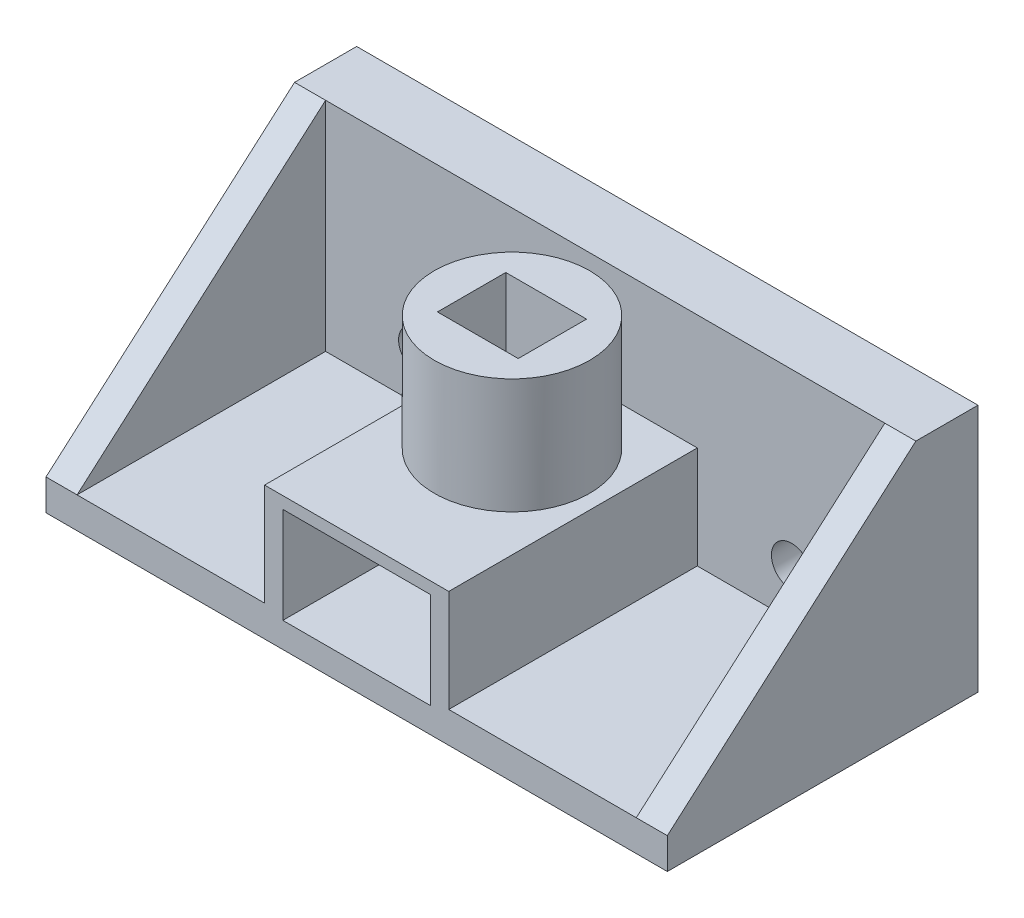
SolidWorks part; units mm, degrees
ref_plane "Front" through (0, 0, 0) normal (0, 0, 1) x (1, 0, 0)
ref_plane "Top" through (0, 0, 0) normal (0, 1, 0) x (1, 0, 0)
ref_plane "Right" through (0, 0, 0) normal (1, 0, 0) x (0, 0, -1)
sketch "Sketch1" plane through (0, 0, 0) normal (0, 1, 0) x (1, 0, 0)
  line L0 (-50, 25) -> (-50, 15)
  line L1 (-50, 25) -> (50, 25)
  line L2 (-50, 25) -> (-50, -25)
  line L3 (-50, -25) -> (50, -25)
  line L4 (50, 25) -> (50, -25)
  line L5 (-50, 25) -> (50, -25) construction
  line L6 (-50, -25) -> (50, 25) construction
  line L7 (-50, 15) -> (50, 15)
  line L8 (50, 15) -> (50, 25)
  line L9 (-50, 25) -> (50, 25)
  line L10 (-50, 15) -> (-50, 25)
  circle A0 centre (0, 0) radius 7.6
  point P0 (0, 0)
  dimension "D3" = 15.2
  dimension "D1" = 100
  dimension "D2" = 50
extrude "Boss-Extrude4" add sketch "Sketch1" along normal blind 5 contours L7 L2 L3 L4 region at (0, 0, -13.923)
sketch "Sketch9" plane through (0, 5, 0) normal (0, 1, 0) x (1, 0, 0)
  circle A0 centre (0, 0) radius 12.5
  dimension "D1" = 25
extrude "Boss-Extrude7" add sketch "Sketch9" along normal blind 35 contours A0
extrude "Extrude-Thin1" add sketch "Sketch1<7>" along normal blind 40 thin contours L1 thin type one direction wall 10
sketch "Sketch1<7>" plane through (0, 0, 0) normal (0, 1, 0) x (1, 0, 0) same geometry as "Sketch1"
sketch "Sketch5" plane through (50, 0, 0) normal (1, 0, 0) x (0, 0, -1)
  line L0 (15, 40) -> (15, 5)
  line L1 (15, 5) -> (-25, 5)
  line L2 (-25, 5) -> (15, 40)
extrude "Boss-Extrude5" add sketch "Sketch5" against normal blind 5
sketch "Sketch6" plane through (-50, 0, 0) normal (-1, 0, 0) x (0, 0, 1)
  line L0 (-15, 40) -> (-15, 5)
  line L1 (-15, 5) -> (25, 5)
  line L2 (25, 5) -> (-15, 40)
extrude "Boss-Extrude6" add sketch "Sketch6" against normal blind 5
sketch "Sketch11" plane through (0, 40, 0) normal (0, 1, 0) x (1, 0, 0)
  line L1 (6.5, -5.5) -> (-6.5, -5.5)
  line L2 (6.5, -5.5) -> (6.5, 5.5)
  line L3 (6.5, 5.5) -> (-6.5, 5.5)
  line L4 (-6.5, -5.5) -> (-6.5, 5.5)
  line L5 (6.5, -5.5) -> (-6.5, 5.5) construction
  line L6 (6.5, 5.5) -> (-6.5, -5.5) construction
  point P0 (0, 0)
  dimension "D1" = 13
  dimension "D2" = 11
extrude "Cut-Extrude2" cut sketch "Sketch11" against normal blind 15
sketch "Sketch13" plane through (0, 0, -25) normal (0, 0, -1) x (-1, 0, 0)
  line L0 (0, 40) -> (0, 12.5)
  line L1 (50, 40) -> (-50, 40) construction
  line L2 (0, 50) -> (0, -50) construction
  line L3 (0, 12.5) -> (30, 12.5)
  line L5 (50, 0) -> (-50, 0) construction
  circle A0 centre (30, 12.5) radius 3.25
  circle A1 centre (-30, 12.5) radius 3.25
  circle A2 centre (30, 12.5) radius 6
  circle A3 centre (-30, 12.5) radius 6
  dimension "D3" = 6.5
  dimension "D4" = 12
  dimension "D1" = 12.5
  dimension "D2" = 30
extrude "Cut-Extrude4" cut sketch "Sketch13<5>" against normal blind 205 contours A0
sketch "Sketch13<5>" plane through (0, 0, -25) normal (0, 0, -1) x (-1, 0, 0) same geometry as "Sketch13"
extrude "Cut-Extrude5" cut sketch "Sketch13" against normal blind 205 contours A1
sketch "Sketch15" plane through (0, 0, -25) normal (0, 0, -1) x (-1, 0, 0)
  line L0 (0, 40) -> (0, 24.3849)
  line L1 (50, 40) -> (-50, 40) construction
  line L2 (0, 50) -> (0, -50) construction
  line L4 (-14.8205, 21.4553) -> (14.8205, 21.4553)
  line L5 (-14.8205, 21.4553) -> (-14.8205, 2.1541)
  line L6 (-14.8205, 2.1541) -> (14.8205, 2.1541)
  line L7 (14.8205, 21.4553) -> (14.8205, 2.1541)
  line L8 (-14.8205, 21.4553) -> (14.8205, 2.1541) construction
  line L9 (-14.8205, 2.1541) -> (14.8205, 21.4553) construction
  line L10 (-11.8829, 19.5424) -> (11.8829, 19.5424)
  line L11 (-11.8829, 19.5424) -> (-11.8829, 4.067)
  line L12 (-11.8829, 4.067) -> (11.8829, 4.067)
  line L13 (11.8829, 19.5424) -> (11.8829, 4.067)
  line L14 (-11.8829, 19.5424) -> (11.8829, 4.067) construction
  line L15 (-11.8829, 4.067) -> (11.8829, 19.5424) construction
  point P7 (0, 11.8047)
  point P12 (0, 11.8047)
extrude "Boss-Extrude11" add sketch "Sketch15" against normal blind 50 contours L7 L4 L5 L6 L10 L13 L12 L11 region at (0, 21.1016, -25)
sketch "Sketch16" plane through (0, 0, -25) normal (0, 0, -1) x (-1, 0, 0)
  line L1 (11.8829, 19.5424) -> (-11.8829, 19.5424)
  line L2 (11.8829, 19.5424) -> (11.8829, 4.067)
  line L3 (11.8829, 4.067) -> (-11.8829, 4.067)
  line L4 (-11.8829, 19.5424) -> (-11.8829, 4.067)
extrude "Cut-Extrude6" cut sketch "Sketch16" against normal blind 66 and the other way blind 32
extrude "Cut-Extrude1" cut sketch "Sketch1<11>" along normal blind 25 contours A0
sketch "Sketch1<11>" plane through (0, 0, 0) normal (0, 1, 0) x (1, 0, 0) same geometry as "Sketch1"
equation "\"52.5.00mm\"=50"
